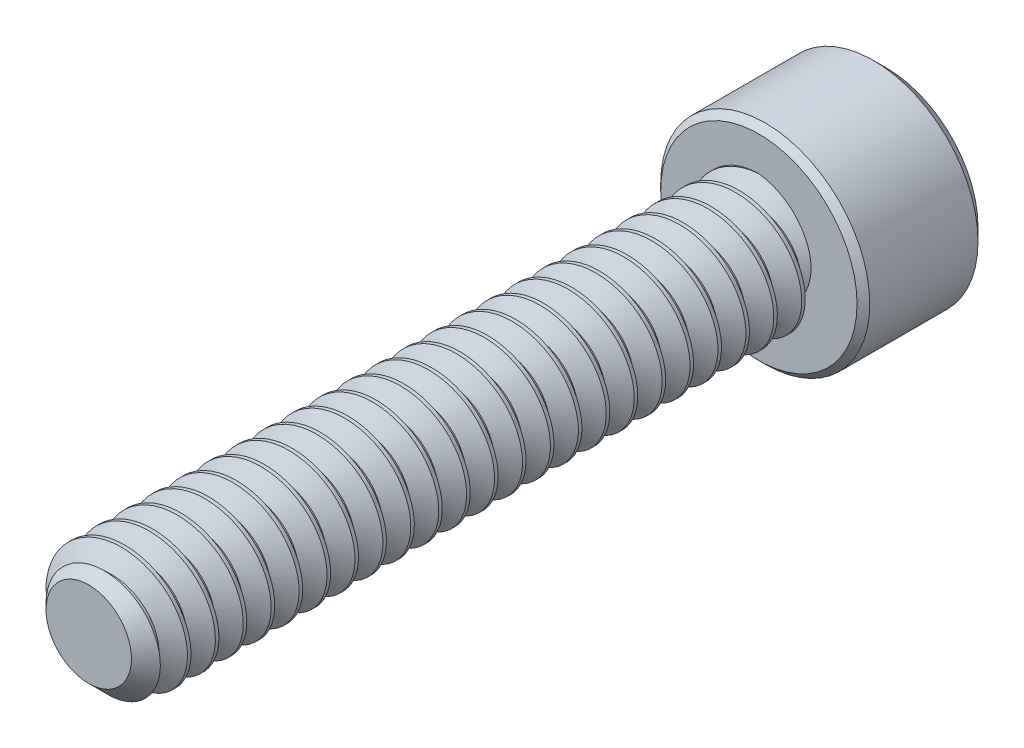
SolidWorks part; units mm, degrees
ref_plane "Front Plane" through (0, 0, 0) normal (0, 0, 1) x (1, 0, 0)
ref_plane "Top Plane" through (0, 0, 0) normal (0, 1, 0) x (1, 0, 0)
ref_plane "Right Plane" through (0, 0, 0) normal (1, 0, 0) x (0, 0, -1)
sketch "Sketch1" plane through (0, 0, 0) normal (0, 0, 1) x (1, 0, 0)
  line L0 (0, 2.413) -> (0, -2.413) construction
  circle A0 centre (0, 0) radius 2.413
  dimension "OD" = 4.826
extrude "Extrude1" add sketch "Sketch1" against normal blind 25.4
sketch "Sketch2" plane through (0, 0, 0) normal (0, 0, 1) x (1, 0, 0)
  circle A0 centre (0, 0) radius 2.413 construction
  circle A1 centre (0, 0) radius 2.413
curve "Helix/Spiral1" pitch 1.0583 height 26.4583 turns 25 parameters "pitch"=1.0583
chamfer "Chamfer3" distance 0.7937 angle 45 1 edges at (2.413, 0, 0)
sketch "Sketch3" plane through (0, 0, 0) normal (1, 0, 0) x (0, 0, -1)
  line L0 (-0.926, 2.413) -> (-0.5292, 1.7256)
  line L1 (-0.5292, 1.7256) -> (-0.3969, 1.7256)
  line L2 (-0.3969, 1.7256) -> (0, 2.413)
  line L3 (-0.926, 2.413) -> (0, 2.413)
  line L4 (-0.463, 2.413) -> (-0.463, 1.7256) construction
  line L5 (-0.7276, 2.0693) -> (-0.1984, 2.0693) construction
  line L6 (0, 2.413) -> (0, -2.413) construction
  dimension "D1" = 0.1323
  dimension "D2" = 0.5292
  dimension "D3" = 60
sweep "Cut-Sweep1" cut profiles "Sketch3" path "Helix/Spiral1"
sketch "Sketch6" plane through (0, 0, -25.4) normal (0, 0, -1) x (-1, 0, 0)
  circle A0 centre (0, 0) radius 3.9624
  dimension "head dia" = 7.9248
extrude "Extrude2" add sketch "Sketch6" along normal blind 4.826
sketch "Sketch7" plane through (0, 0, -30.226) normal (0, 0, -1) x (-1, 0, 0)
  line L1 (0, 2.2914) -> (-1.9844, 1.1457)
  line L2 (-1.9844, 1.1457) -> (-1.9844, -1.1457)
  line L3 (-1.9844, -1.1457) -> (0, -2.2914)
  line L4 (0, -2.2914) -> (1.9844, -1.1457)
  line L5 (1.9844, -1.1457) -> (1.9844, 1.1457)
  line L6 (1.9844, 1.1457) -> (0, 2.2914)
  circle A0 centre (0, 0) radius 1.9844 construction
  dimension "hex dia" = 3.9688
extrude "Cut-Extrude1" cut sketch "Sketch7" against normal blind 2.9766
sketch "Sketch8" plane through (0, 0, -30.226) normal (0, 0, -1) x (-1, 0, 0)
  circle A0 centre (0, 0) radius 2.2914
extrude "Cut-Extrude2" cut sketch "Sketch8" against normal blind 0.4826 draft 45
chamfer "Chamfer1" distance 0.4826 angle 45 1 edges at (-3.9624, 0, -30.226)
chamfer "Chamfer2" distance 0.2413 angle 45 1 edges at (-3.9624, 0, -25.4)
sketch "Sketch9" plane through (0, 0, 0) normal (1, 0, 0) x (0, 0, -1)
  line L0 (0, 2.413) -> (0, -2.413) construction
  line L1 (5.8208, 2.413) -> (5.8208, -2.413) construction
  line L2 (25.4, 3.9624) -> (25.4, -3.9624) construction
  line L3 (30.226, 3.9624) -> (30.226, -3.9624) construction
  line L4 (30.226, 0) -> (0, 0) construction
  dimension "D1" = 5.8208
  dimension "D2" = 4.826
  dimension "D3" = 7.9248
  dimension "D4" = 25.4
equation "\"D3@Helix/Spiral1\" = \"screw length@Extrude1\"+\"pitch@Helix/Spiral1\""
equation "\"D1@Sketch3\" = \"pitch@Helix/Spiral1\"*.125"
equation "\"D2@Sketch3\" = \"pitch@Helix/Spiral1\"*.5"
equation "\"D1@Cut-Extrude1\" = \"hex dia@Sketch7\"*.75"
equation "\"D1@Chamfer1\" = \"head depth@Extrude2\"/10"
equation "\"D1@Sketch9\" = \"pitch@Helix/Spiral1\"*5.5"
equation "\"D1@Chamfer2\" = \"D1@Chamfer1\"/2"
equation "\"D1@Cut-Extrude2\" = \"D1@Chamfer2\"*2"
equation "\"D1@Chamfer3\" = \"pitch@Helix/Spiral1\"*.750"
equation "\"D2@Sketch9\" = \"head depth@Extrude2\""
equation "\"D3@Sketch9\" = \"head dia@Sketch6\""
equation "\"D4@Sketch9\" = \"screw length@Extrude1\""
